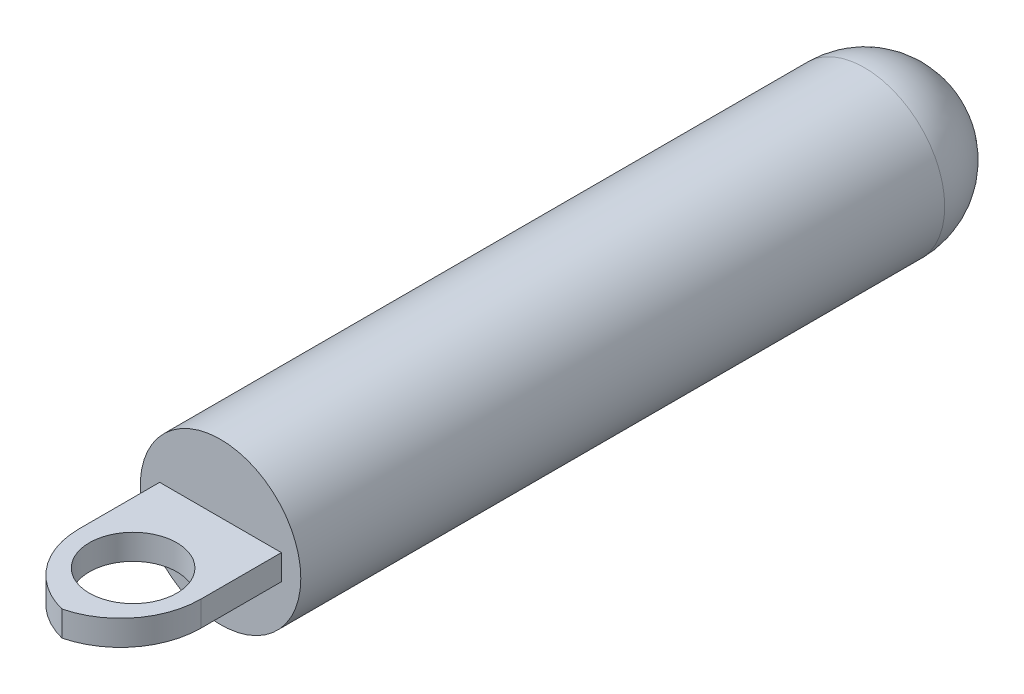
SolidWorks part; units mm, degrees
material "Alloy Steel"
ref_plane "Front Plane" through (0, 0, 0) normal (0, 0, 1) x (1, 0, 0)
ref_plane "Top Plane" through (0, 0, 0) normal (0, 1, 0) x (1, 0, 0)
ref_plane "Right Plane" through (0, 0, 0) normal (1, 0, 0) x (0, 0, -1)
sketch "Sketch1" plane through (0, 0, 0) normal (0, 0, 1) x (1, 0, 0)
  circle A0 centre (0, 0) radius 1.995
  dimension "D1" = 3.99
extrude "Boss-Extrude1" add sketch "Sketch1" along normal blind 16
dome "Dome1" faces to dome 1 distance 2 reverse direction no elliptical dome no face at (1.995, 0, 0) parameters "D1"=2
sketch "Sketch2" plane through (0, 0, 16) normal (0, 0, 1) x (1, 0, 0)
  line L1 (-1.5127, 0.3133) -> (1.5127, 0.3133)
  line L2 (-1.5127, 0.3133) -> (-1.5127, -0.3133)
  line L3 (-1.5127, -0.3133) -> (1.5127, -0.3133)
  line L4 (1.5127, 0.3133) -> (1.5127, -0.3133)
  line L5 (-1.5127, 0.3133) -> (1.5127, -0.3133) construction
  line L6 (-1.5127, -0.3133) -> (1.5127, 0.3133) construction
  point P0 (0, 0)
extrude "Boss-Extrude2" add sketch "Sketch2" along normal blind 4
fillet "Fillet1" radius 2 2 edges at (-1.5127, 0, 20) (1.5127, 0, 20)
sketch "Sketch3" plane through (0, 0.3133, 0) normal (0, 1, 0) x (1, 0, 0)
  circle A0 centre (0, -18.172) radius 1.0865
extrude "Cut-Extrude1" cut sketch "Sketch3" against normal blind 4
